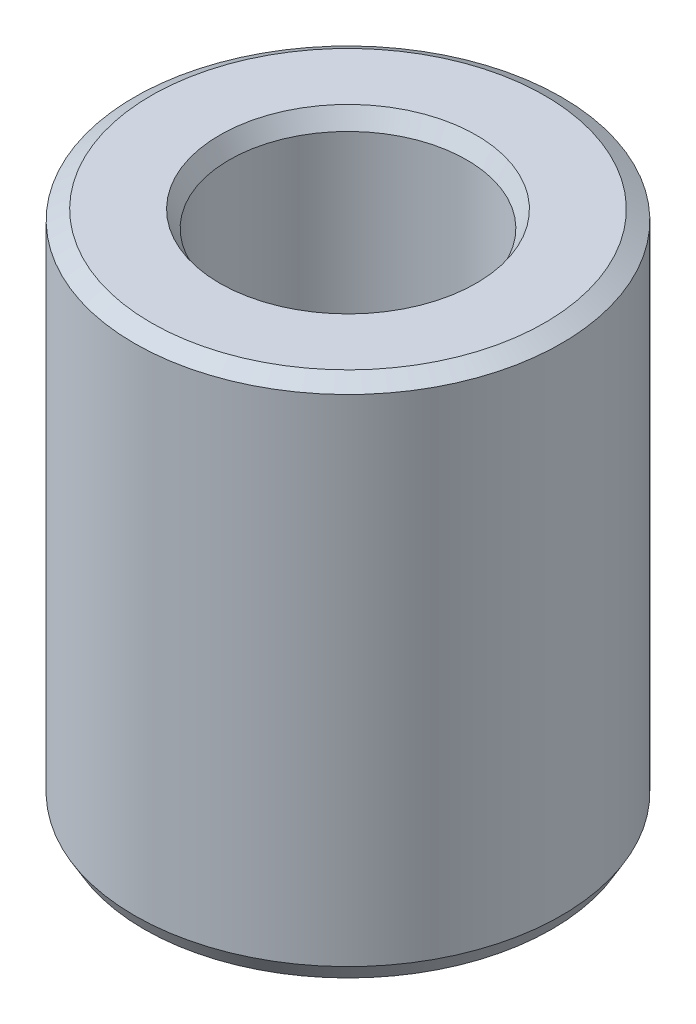
SolidWorks part; units mm, degrees
ref_plane "Front Plane" through (0, 0, 0) normal (0, 0, 1) x (1, 0, 0)
ref_plane "Top Plane" through (0, 0, 0) normal (0, 1, 0) x (1, 0, 0)
ref_plane "Right Plane" through (0, 0, 0) normal (1, 0, 0) x (0, 0, -1)
sketch "Sketch1" plane through (0, 0, 0) normal (0, 1, 0) x (1, 0, 0)
  circle A0 centre (0, 0) radius 35
  dimension "SLEEVE_OD" = 70
extrude "Boss-Extrude1" add sketch "Sketch1" along normal blind 85.5414
sketch "Sketch2" plane through (0, 0, 0) normal (0, 1, 0) x (1, 0, 0)
  circle A0 centre (0, 0) radius 19.4681
  dimension "BORE_D" = 38.9363
extrude "Cut-Extrude1" cut sketch "Sketch2" along normal through all
chamfer "Chamfer1" distance 1.5736 angle 60 4 edges at (0, 85.5414, 19.4681) (0, 0, 19.4681) (0, 0, 35) (0, 85.5414, 35) first distance on face at (0, 85.5414, 19.4681) first distance on face at (0, 0, 19.4681) first distance on face at (0, 85.5414, 35)
